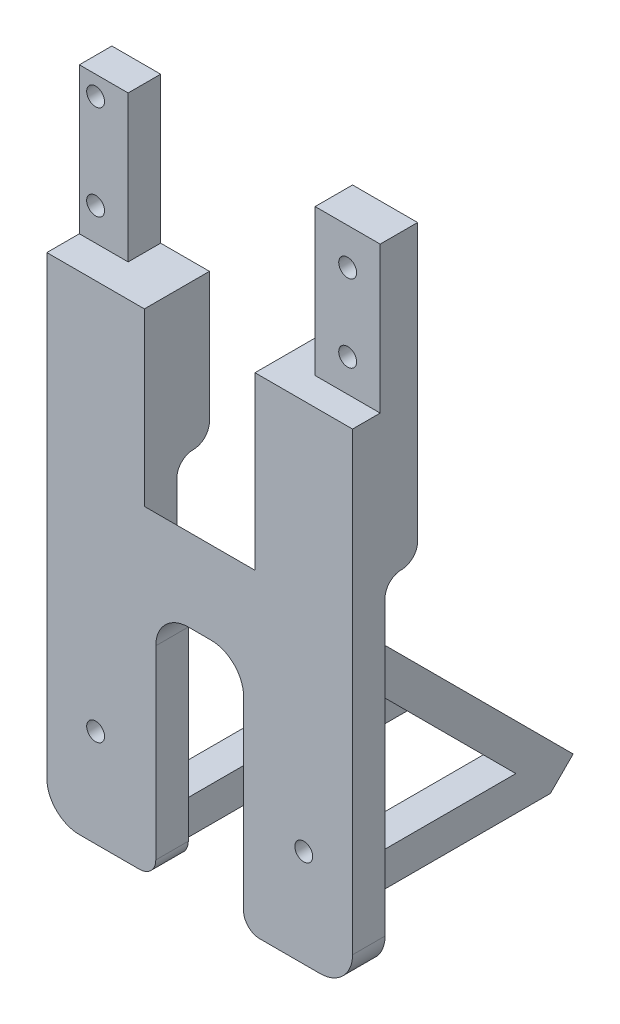
SolidWorks part; units mm, degrees
ref_plane "Front Plane" through (0, 0, 0) normal (0, 0, 1) x (1, 0, 0)
ref_plane "Top Plane" through (0, 0, 0) normal (0, 1, 0) x (1, 0, 0)
ref_plane "Right Plane" through (0, 0, 0) normal (1, 0, 0) x (0, 0, -1)
sketch "Sketch2" plane through (0, 0, 0) normal (0, 0, 1) x (1, 0, 0)
  line L0 (44, -75) -> (74, -75)
  line L1 (74, -75) -> (74, -225)
  line L2 (10, -75) -> (-20, -75)
  line L3 (10, -75) -> (-27.5, -75) construction
  line L4 (-20, -75) -> (-20, -225)
  line L5 (44, -75) -> (44, -225)
  line L6 (10, -75) -> (10, -225)
  line L7 (10, -225) -> (-20, -225)
  line L8 (44, -225) -> (74, -225)
  line L9 (10, -225) -> (44, -225)
  line L10 (10, -205) -> (44, -205)
  line M11 (-27.5, -75) -> (10, -75)
  dimension "D1" = 30
  dimension "D2" = 150
  dimension "D3" = 150
  dimension "D4" = 150
  dimension "D5" = 20
extrude "Boss-Extrude1" add sketch "Sketch2" against normal up to surface (10 mm away) contours L7 L6 L4 M11 | L10 L6 L9 L5 | L5 L8 L1 L0
sketch "Sketch3" plane through (0, 0, -8.5) normal (0, 0, -1) x (-1, 0, 0)
  line L0 (-74, -75) -> (-74, -30)
  line L1 (-74, -30) -> (-54, -30)
  line L4 (-54, -75) -> (-54, -7.2161)
  line L5 (-54, -7.2161) -> (-74, -7.2161)
  line L6 (-74, -7.2161) -> (-74, -75)
  line L7 (-74, -75) -> (-54, -75)
  line L8 (-54, -75) -> (-54, -7.2161)
  line L9 (-54, -7.2161) -> (-74, -7.2161)
  line L10 (-74, -7.2161) -> (-74, -75)
  line L11 (-74, -75) -> (-54, -75)
  circle M6 centre (-64, -65) radius 2.75
  line M7 (-54, -75) -> (-54, -7.2161)
  line M9 (-74, -7.2161) -> (-74, -75)
  line M10 (-74, -75) -> (-54, -75)
  circle M12 centre (-64, -41.25) radius 2.75
  dimension "D2" = 45
  dimension "D1" = 0
extrude "Boss-Extrude2" add sketch "Sketch3" along normal up to surface (1.5 mm away) contours L1 M9 M10 M7 M12 M6 up to face at (27, -145, -10)
sketch "Sketch4" plane through (0, 0, -10) normal (0, 0, -1) x (-1, 0, 0)
  line L0 (5, -30) -> (20, -30)
  line L1 (20, -75) -> (20, -30)
  line L2 (5, -75) -> (-10, -75)
  line L3 (-10, -75) -> (-10, -120)
  line L4 (-10, -75) -> (-10, -205) construction
  line L5 (-10, -120) -> (20, -120)
  line L6 (20, -75) -> (20, -225) construction
  line L7 (20, -120) -> (20, -75)
  line L16 (5, -75) -> (27.5, -75)
  line L17 (35, -67.5) -> (35, -62.5)
  line L18 (42.5, -55) -> (55, -55)
  line L19 (55, -55) -> (55, -5.6569)
  line L20 (55, -5.6569) -> (55, 5.6569)
  line L21 (55, 5.6569) -> (55, 55)
  line L22 (55, 55) -> (5, 55)
  line L23 (5, 55) -> (5, 8.6789)
  line L24 (5, 8.6789) -> (25, 8.6789)
  line L25 (25, 8.6789) -> (25, 37.5)
  line L26 (32.5, 45) -> (37.5, 45)
  line L27 (45, 37.5) -> (45, -37.5)
  line L28 (37.5, -45) -> (32.5, -45)
  line L29 (25, -37.5) -> (25, -8.6789)
  line L30 (25, -8.6789) -> (5, -8.6789)
  line L31 (5, -8.6789) -> (5, -75)
  line L32 (5, -75) -> (20, -75)
  line L47 (5, -30) -> (5, -75)
  circle A0 centre (15, -65) radius 2.75 construction
  circle A1 centre (15, -65) radius 2.75
  circle A2 centre (15, -35.9197) radius 2.75 construction
  circle A3 centre (15, -35.9197) radius 2.75
  arc A6 (27.5, -75) -> (35, -67.5) centre (27.5, -67.5) ccw
  arc A7 (42.5, -55) -> (35, -62.5) centre (42.5, -62.5) ccw
  arc A8 (32.5, 45) -> (25, 37.5) centre (32.5, 37.5) ccw
  arc A9 (45, 37.5) -> (37.5, 45) centre (37.5, 37.5) ccw
  arc A10 (37.5, -45) -> (45, -37.5) centre (37.5, -37.5) ccw
  arc A11 (25, -37.5) -> (32.5, -45) centre (32.5, -37.5) ccw
  line M28 (20, -225) -> (20, -75)
  line M29 (20, -75) -> (-10, -75)
  line M30 (-10, -75) -> (-10, -205)
  dimension "D2" = 45
  dimension "D1" = 0
extrude "Boss-Extrude3" add sketch "Sketch4" along normal blind 10 contours L5 M30 M28 M29 | L0 L47 L1 A3 A1 M29
sketch "Sketch5" plane through (0, 0, -10) normal (0, 0, -1) x (-1, 0, 0)
  line L0 (-44, -120) -> (-74, -120)
  line L10 (20, -120) -> (-10, -120)
  line L11 (-10, -120) -> (-10, -205)
  line L12 (-10, -205) -> (-44, -205)
  line L13 (-44, -205) -> (-44, -75)
  line L14 (-44, -75) -> (-54, -75)
  line L15 (-54, -75) -> (-54, -30)
  line L16 (-54, -30) -> (-74, -30)
  line L17 (-74, -30) -> (-74, -225)
  line L18 (-74, -225) -> (20, -225)
  line L19 (20, -225) -> (20, -120)
  line L22 (-10, -205) -> (-44, -205)
  line L23 (-44, -120) -> (-44, -75)
  line L24 (-44, -75) -> (-54, -75)
  line L25 (-54, -75) -> (-54, -30)
  line L26 (-54, -30) -> (-74, -30)
  line L27 (-74, -30) -> (-74, -120)
  line L28 (-74, -225) -> (20, -225)
  circle A0 centre (-64, -41.25) radius 2.75 construction
  circle A1 centre (-64, -65) radius 2.75 construction
  circle A2 centre (-64, -41.25) radius 2.75
  circle A3 centre (-64, -65) radius 2.75
  line M14 (-44, -205) -> (-44, -75)
  line M15 (-44, -75) -> (-54, -75)
  line M16 (-54, -75) -> (-54, -30)
  line M17 (-54, -30) -> (-74, -30)
  line M18 (-74, -30) -> (-74, -225)
  circle M21 centre (-64, -65) radius 2.75
  circle M22 centre (-64, -41.25) radius 2.75
  dimension "D1" = 0
extrude "Boss-Extrude4" add sketch "Sketch5" along normal blind 10 contours L0 M14 M15 M16 M17 M18 M21 M22
fillet "Fillet1" radius 5 4 edges at (59, -120, -10) (59, -120, -20) (-5, -120, -10) (-5, -120, -20)
sketch "Sketch6" plane through (0, -205, 0) normal (0, 1, 0) x (1, 0, 0)
  line L4 (44, 10) -> (10, 10)
  line L5 (10, 10) -> (10, 0)
  line L6 (10, 0) -> (44, 0)
  line L7 (44, 0) -> (44, 10)
  line L8 (44, 10) -> (10, 10)
  line L9 (10, 10) -> (10, 0)
  line L10 (10, 0) -> (44, 0)
  line L11 (44, 0) -> (44, 10)
  dimension "D1" = 0
extrude "Boss-Extrude5" add sketch "Sketch6" along normal blind 70
sketch "Sketch7" plane through (-20, 0, 0) normal (-1, 0, 0) x (0, 0, 1)
  line L0 (-109.75, -90) -> (-107, -87.25)
  line L1 (-108.375, -88.625) -> (-108.9445, -88.0555)
  line L2 (-108.9445, -88.0555) -> (-52.376, -144.624)
  line L3 (-52.376, -144.624) -> (-11.7204, -103.9684)
  line L4 (-34.6983, -162.3017) -> (0, -127.6033)
  line L5 (-34.6983, -162.3017) -> (-45.3049, -172.9083)
  line L7 (-45.3049, -172.9083) -> (0, -172.9083)
  line L8 (0, -75) -> (0, -225) construction
  line L9 (0, -172.9083) -> (0, -127.6033)
  line L10 (-34.6983, -162.3017) -> (5.9573, -121.646) construction
  circle A0 centre (-107, -90) radius 2.75 construction
  circle A2 centre (-107, -90) radius 2.75
  line M7 (-10, -125) -> (-10, -225)
  line M9 (0, -225) -> (0, -75)
  dimension "D1" = 80
  dimension "D3" = 15
  dimension "D2" = 25
extrude "Boss-Extrude6" add sketch "Sketch7" against normal up to surface (94 mm away) contours L5 L7 L4 M7 | L7 L4 M7 M9 up to face at (74, -113.3333, -10.2222)
sketch "Sketch8" plane through (44, 0, 0) normal (-1, 0, 0) x (0, 0, 1)
  line L0 (-7.3967, -135) -> (-10.0869, -137.6903)
  line L1 (-10.0869, -137.6903) -> (-10, -135)
  line L2 (-10, -135) -> (-7.3967, -135)
extrude "Cut-Extrude1" cut sketch "Sketch8" along normal up to surface (34 mm away) up to face at (10, -113.4504, -10.2996)
fillet "Fillet2" radius 5 1 edges at (27, -172.9083, -45.3049)
sketch "Sketch9" plane through (-20, 0, 0) normal (-1, 0, 0) x (0, 0, 1)
  line L0 (-10, -172.9083) -> (-10, -137.6033)
  line L10 (-10, -137.6033) -> (-36.7694, -164.3727)
  line L11 (-33.2339, -172.9083) -> (-10, -172.9083)
  line L12 (-10, -172.9083) -> (-10, -225)
  line L13 (-10, -225) -> (0, -225)
  line L14 (0, -225) -> (0, -75)
  line L15 (0, -75) -> (-10, -75)
  line L16 (-10, -75) -> (-10, -30)
  line L17 (-10, -30) -> (-20, -30)
  line L18 (-20, -30) -> (-20, -115)
  line L19 (-10, -125) -> (-10, -137.6033)
  line L20 (-10, -137.6033) -> (-36.7694, -164.3727)
  line L21 (-33.2339, -172.9083) -> (-10, -172.9083)
  line L22 (-10, -172.9083) -> (-10, -225)
  line L23 (-10, -225) -> (0, -225)
  line L24 (0, -225) -> (0, -75)
  line L25 (0, -75) -> (-10, -75)
  line L26 (-10, -75) -> (-10, -30)
  line L27 (-10, -30) -> (-20, -30)
  line L28 (-20, -30) -> (-20, -115)
  line L29 (-10, -125) -> (-10, -137.6033)
  arc A3 (-36.7694, -164.3727) -> (-33.2339, -172.9083) centre (-33.2339, -167.9083) ccw
  arc A4 (-20, -115) -> (-15, -120) centre (-15, -115) ccw
  arc A5 (-10, -125) -> (-15, -120) centre (-15, -125) ccw
  arc A6 (-36.7694, -164.3727) -> (-33.2339, -172.9083) centre (-33.2339, -167.9083) ccw
  arc A7 (-20, -115) -> (-15, -120) centre (-15, -115) ccw
  arc A8 (-10, -125) -> (-15, -120) centre (-15, -125) ccw
  line M14 (-10, -137.6033) -> (-36.7694, -164.3727)
  arc M15 (-36.7694, -164.3727) -> (-33.2339, -172.9083) centre (-33.2339, -167.9083) ccw
  line M16 (-33.2339, -172.9083) -> (-10, -172.9083)
  dimension "D1" = 0
extrude "Cut-Extrude2" cut sketch "Sketch9" against normal blind 20 contours L0 M16 M14 M15
sketch "Sketch10" plane through (74, 0, 0) normal (1, 0, 0) x (0, 0, -1)
  line L0 (10, -137.6033) -> (10, -172.9083)
  line L10 (10, -172.9083) -> (33.2339, -172.9083)
  line L11 (36.7694, -164.3727) -> (10, -137.6033)
  line L12 (10, -137.6033) -> (10, -125)
  line L13 (20, -115) -> (20, -30)
  line L14 (20, -30) -> (8.5, -30)
  line L15 (8.5, -30) -> (8.5, -75)
  line L16 (8.5, -75) -> (0, -75)
  line L17 (0, -75) -> (0, -225)
  line L18 (0, -225) -> (10, -225)
  line L19 (10, -225) -> (10, -172.9083)
  line L20 (10, -172.9083) -> (33.2339, -172.9083)
  line L21 (36.7694, -164.3727) -> (10, -137.6033)
  line L22 (10, -137.6033) -> (10, -125)
  line L23 (20, -115) -> (20, -30)
  line L24 (20, -30) -> (8.5, -30)
  line L25 (8.5, -30) -> (8.5, -75)
  line L26 (8.5, -75) -> (0, -75)
  line L27 (0, -75) -> (0, -225)
  line L28 (0, -225) -> (10, -225)
  line L29 (10, -225) -> (10, -172.9083)
  arc A3 (33.2339, -172.9083) -> (36.7694, -164.3727) centre (33.2339, -167.9083) ccw
  arc A4 (15, -120) -> (10, -125) centre (15, -125) ccw
  arc A5 (15, -120) -> (20, -115) centre (15, -115) ccw
  arc A6 (33.2339, -172.9083) -> (36.7694, -164.3727) centre (33.2339, -167.9083) ccw
  arc A7 (15, -120) -> (10, -125) centre (15, -125) ccw
  arc A8 (15, -120) -> (20, -115) centre (15, -115) ccw
  line M14 (10, -172.9083) -> (33.2339, -172.9083)
  arc M15 (33.2339, -172.9083) -> (36.7694, -164.3727) centre (33.2339, -167.9083) ccw
  line M16 (36.7694, -164.3727) -> (10, -137.6033)
  dimension "D1" = 0
extrude "Cut-Extrude3" cut sketch "Sketch10" against normal blind 20 contours L0 M16 M14 M15
sketch "Sketch12" plane through (0, 0, 0) normal (-1, 0, 0) x (0, 0, 1)
  line L0 (-10, -137.6033) -> (22.7164, -106.7062)
  line L1 (22.7164, -106.7062) -> (36.4485, -121.2468)
  line L2 (36.4485, -121.2468) -> (-10, -165.1125)
  line L3 (-10, -125) -> (-10, -225) construction
  line L4 (-10, -165.1125) -> (-10, -137.6033)
  dimension "D1" = 45
  dimension "D2" = 20
extrude "Boss-Extrude7" add sketch "Sketch12" against normal up to surface (54 mm away) up to face at (54, -162.2434, -23.2137)
sketch "Sketch13" plane through (54, 0, 0) normal (1, 0, 0) x (0, 0, -1)
  line L0 (10, -165.6685) -> (17.2397, -172.9083)
  line L3 (36.7694, -164.3727) -> (10, -137.6033)
  line L4 (10, -137.6033) -> (10, -172.9083)
  line L5 (10, -172.9083) -> (33.2339, -172.9083)
  line L7 (10, -165.6685) -> (10, -172.9083)
  line L8 (10, -172.9083) -> (17.2397, -172.9083)
  arc A1 (33.2339, -172.9083) -> (36.7694, -164.3727) centre (33.2339, -167.9083) ccw
  arc A2 (33.2339, -172.9083) -> (36.7694, -164.3727) centre (33.2339, -167.9083) ccw
  line M6 (10, -137.6033) -> (10, -172.9083)
  line M7 (10, -172.9083) -> (33.2339, -172.9083)
  dimension "D1" = 0
extrude "Cut-Extrude4" cut sketch "Sketch13" against normal through all both and the other way through all contours L0 M6 M7
sketch "Sketch14" plane through (54, 0, 0) normal (1, 0, 0) x (0, 0, -1)
  line L4 (-36.4485, -121.2468) -> (0, -155.6685)
  line L5 (0, -155.6685) -> (0, -128.1594)
  line L6 (0, -128.1594) -> (-22.7164, -106.7062)
  line L7 (-22.7164, -106.7062) -> (-36.4485, -121.2468)
  line L8 (-36.4485, -121.2468) -> (0, -155.6685)
  line L9 (0, -155.6685) -> (0, -128.1594)
  line L10 (0, -128.1594) -> (-22.7164, -106.7062)
  line L11 (-22.7164, -106.7062) -> (-36.4485, -121.2468)
  dimension "D1" = 0
extrude "Cut-Extrude5" cut sketch "Sketch14" against normal through all both
sketch "Sketch15" plane through (54, 0, 0) normal (1, 0, 0) x (0, 0, -1)
  line L0 (17.2397, -172.9083) -> (56.1306, -211.7991)
  line L1 (36.7694, -164.3727) -> (70.1632, -197.7666)
  line L2 (56.1306, -211.7991) -> (70.1632, -197.7666)
  line L3 (17.2397, -172.9083) -> (33.2339, -172.9083) construction
  line L4 (17.2397, -172.9083) -> (33.2339, -172.9083)
  arc A0 (33.2339, -172.9083) -> (36.7694, -164.3727) centre (33.2339, -167.9083) ccw construction
  arc A1 (33.2339, -172.9083) -> (36.7694, -164.3727) centre (33.2339, -167.9083) ccw
  dimension "D1" = 55
extrude "Boss-Extrude8" add sketch "Sketch15" against normal up to surface (54 mm away) up to face at (0, -162.9285, -22.0189)
sketch "Sketch16" plane through (54, 0, 0) normal (1, 0, 0) x (0, 0, -1)
  line L0 (63.1469, -204.7828) -> (10, -151.6359)
  line L1 (56.1306, -211.7991) -> (70.1632, -197.7666) construction
  line L2 (10, -125) -> (10, -225) construction
  line L7 (10, -137.6033) -> (10, -165.6685)
  line L8 (10, -165.6685) -> (56.1306, -211.7991)
  line L9 (56.1306, -211.7991) -> (70.1632, -197.7666)
  line L10 (70.1632, -197.7666) -> (10, -137.6033)
  line L11 (10, -151.6359) -> (10, -165.6685)
  line L12 (10, -165.6685) -> (56.1306, -211.7991)
  line L13 (56.1306, -211.7991) -> (63.1469, -204.7828)
  dimension "D1" = 0
extrude "Cut-Extrude6" cut sketch "Sketch16" against normal through all both and the other way through all contours L11 L12 L13 L0
sketch "Sketch18" plane through (0, -63.8017, 63.8017) normal (0, 0.7071, -0.7071) x (1, 0, 0)
  line L0 (27, 139.3) -> (27, 132.3) construction
  line L1 (32, 139.3) -> (22, 139.3) construction
  line L2 (27, 139.3) -> (27, 146.3) construction
  line L3 (27, 139.3) -> (27, 142.3)
  line L4 (27, 139.3) -> (27, 136.3)
  line L5 (27, 142.3) -> (27, 146.3)
  line L6 (27, 136.3) -> (27, 132.3)
  circle A0 centre (27, 144.3) radius 2.2
  circle A1 centre (27, 134.3) radius 2.2
  dimension "D5" = 4.4
  dimension "D6" = 4.4
  dimension "D1" = 7
  dimension "D2" = 7
  dimension "D3" = 3
  dimension "D4" = 3
extrude "Cut-Extrude7" cut sketch "Sketch18" against normal up to surface (9.9225 mm away) up to face at (27, -178.2094, -36.5735)
sketch "Sketch20" plane through (0, -133.9649, -133.9649) normal (0, -0.7071, -0.7071) x (1, 0, 0)
  line L4 (54, 100.1517) -> (0, 100.1517)
  line L5 (0, 100.1517) -> (0, 90.2292)
  line L6 (0, 90.2292) -> (54, 90.2292)
  line L7 (54, 90.2292) -> (54, 100.1517)
  line L8 (54, 100.1517) -> (0, 100.1517)
  line L9 (0, 100.1517) -> (0, 90.2292)
  line L10 (0, 90.2292) -> (54, 90.2292)
  line L11 (54, 90.2292) -> (54, 100.1517)
  dimension "D1" = 0
extrude "Boss-Extrude9" add sketch "Sketch20" along normal blind 25
sketch "Sketch21" plane through (0, -63.8017, 63.8017) normal (0, 0.7071, -0.7071) x (1, 0, 0)
  line L0 (27, 146.5) -> (27, 186.5)
  line L1 (27, 186.5) -> (27, 190.9) construction
  line L2 (27, 190.9) -> (27, 197.4)
  line L3 (27, 197.4) -> (27, 201.8) construction
  circle A0 centre (27, 144.3) radius 2.2 construction
  circle A2 centre (27, 199.6) radius 2.2
  circle A3 centre (27, 188.7) radius 2.2
  line M13 (54, 104.3713) -> (54, 214.455)
  dimension "D1" = 40
  dimension "D2" = 4.4
  dimension "D3" = 6.5
  dimension "D4" = 4.4
extrude "Cut-Extrude8" cut sketch "Sketch21" against normal blind 25 contours A2 | A3 M13
sketch "Sketch22" plane through (0, -63.8017, 63.8017) normal (0, 0.7071, -0.7071) x (1, 0, 0)
  line L0 (27, 201.8) -> (27, 205.8)
  line L1 (27, 205.8) -> (33.5, 205.8)
  line L2 (27, 205.8) -> (20.5, 205.8)
  line L3 (27, 132.1) -> (27, 128.1)
  line L4 (33.5, 205.8) -> (33.5, 128.1)
  line L5 (27, 128.1) -> (33.5, 128.1)
  line L6 (27, 128.1) -> (20.5, 128.1)
  line L7 (20.5, 205.8) -> (20.5, 128.1)
  circle A0 centre (27, 199.6) radius 2.2 construction
  circle A1 centre (27, 134.3) radius 2.2 construction
  dimension "D1" = 4
  dimension "D2" = 6.5
  dimension "D3" = 6.5
  dimension "D4" = 4
extrude "Boss-Extrude10" add sketch "Sketch22" along normal blind 13
sketch "Sketch23" plane through (0, -54.6093, 54.6093) normal (0, 0.7071, -0.7071) x (1, 0, 0)
  line L4 (20.5, 128.1) -> (33.5, 128.1)
  line L5 (33.5, 128.1) -> (33.5, 205.8)
  line L6 (33.5, 205.8) -> (20.5, 205.8)
  line L7 (20.5, 205.8) -> (20.5, 128.1)
  line L8 (20.5, 128.1) -> (33.5, 128.1)
  line L9 (33.5, 128.1) -> (33.5, 205.8)
  line L10 (33.5, 205.8) -> (20.5, 205.8)
  line L11 (20.5, 205.8) -> (20.5, 128.1)
  dimension "D1" = 0
extrude "Cut-Extrude10" cut sketch "Sketch23" against normal up to surface (13 mm away) up to face at (27, -181.8532, -54.2498)
sketch "Sketch24" plane through (0, -63.8017, 63.8017) normal (0, 0.7071, -0.7071) x (1, 0, 0)
  line L0 (13.5, 153.1) -> (40.5, 153.1)
  line L5 (40.5, 153.1) -> (40.5, 126.1)
  line L6 (13.5, 126.1) -> (40.5, 126.1)
  line L7 (13.5, 153.1) -> (13.5, 126.1)
extrude "Cut-Extrude11" cut sketch "Sketch24" against normal blind 10
sketch "Sketch25" plane through (0, 0, -10) normal (0, 0, -1) x (-1, 0, 0)
  line L0 (-40.5, -152.9679) -> (-40.5, -233.312)
  line L1 (-13.5, -152.9679) -> (-13.5, -234.0234)
  line L2 (-13.5, -234.0234) -> (-40.5, -233.312)
  line L3 (-13.5, -152.9679) -> (-40.5, -152.9679) construction
  line L4 (-13.5, -152.9679) -> (-40.5, -152.9679)
extrude "Cut-Extrude12" cut sketch "Sketch25" against normal blind 10
sketch "Sketch26" plane through (54, 0, 0) normal (1, 0, 0) x (0, 0, -1)
  line L0 (80.8246, -222.4605) -> (6.6382, -222.4605)
  line L1 (80.8246, -222.4605) -> (70.218, -211.8539)
  line L2 (80.8246, -222.4605) -> (10, -151.6359) construction
  line L3 (70.218, -211.8539) -> (3.6971, -211.8539)
  line L4 (3.6971, -211.8539) -> (3.6971, -222.4605)
  line L5 (3.6971, -222.4605) -> (6.6382, -222.4605)
  dimension "D1" = 15
extrude "Boss-Extrude11" add sketch "Sketch26" against normal blind 10
sketch "Sketch27" plane through (0, 0, 0) normal (-1, 0, 0) x (0, 0, 1)
  line L4 (-10, -222.4605) -> (-10, -211.8539)
  line L5 (-10, -211.8539) -> (-70.218, -211.8539)
  line L6 (-70.218, -211.8539) -> (-80.8246, -222.4605)
  line L7 (-80.8246, -222.4605) -> (-10, -222.4605)
  line L8 (-10, -222.4605) -> (-10, -211.8539)
  line L9 (-10, -211.8539) -> (-70.218, -211.8539)
  line L10 (-70.218, -211.8539) -> (-80.8246, -222.4605)
  line L11 (-80.8246, -222.4605) -> (-10, -222.4605)
  dimension "D1" = 0
extrude "Boss-Extrude12" add sketch "Sketch27" against normal blind 10
fillet "Fillet3" radius 10 2 edges at (-20, -225, -5) (74, -225, -5)
fillet "Fillet4" radius 5 2 edges at (13.5, -225, -5) (40.5, -225, -5)
fillet "Fillet5" radius 10 2 edges at (40.5, -152.9679, -5) (13.5, -152.9679, -5)
sketch "Sketch28" plane through (0, 0, -10) normal (0, 0, -1) x (-1, 0, 0)
  line L0 (-74, -170) -> (-74, -195)
  line L1 (-74, -125) -> (-74, -215) construction
  line L2 (-74, -195) -> (20, -195) construction
  line L3 (20, -125) -> (20, -215) construction
  line L4 (-74, -195) -> (-59, -195)
  line L5 (20, -195) -> (5, -195)
  circle A0 centre (5, -195) radius 2.75
  circle A1 centre (-59, -195) radius 2.75
  dimension "D4" = 5.5
  dimension "D1" = 25
  dimension "D2" = 15
  dimension "D3" = 15
extrude "Cut-Extrude14" cut sketch "Sketch28" against normal through all contours L4 L2 A1 | L2 L4 A1 | A0 L2 L5 | L2 A0 L5
